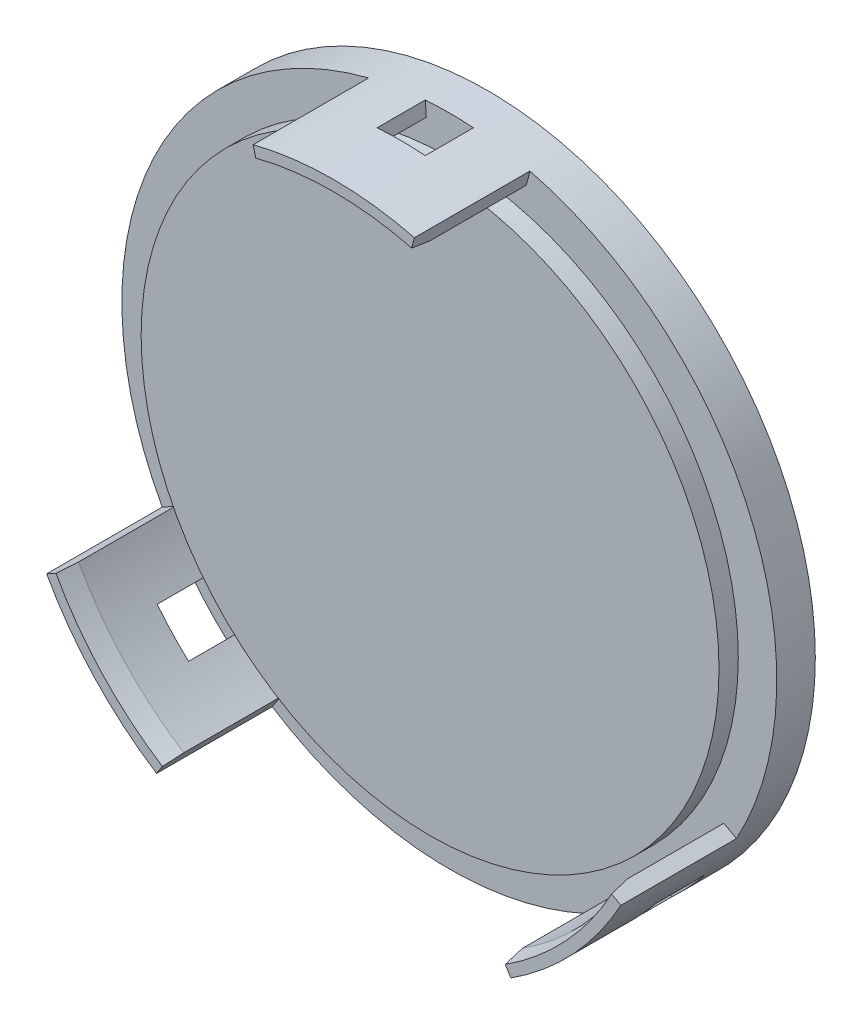
SolidWorks part; units mm, degrees
note: The reader was unsure of these and kept them because the rebuilt part matched: shared geometry of "Sketch1<2>".
ref_plane "Front Plane" through (0, 0, 0) normal (0, 0, 1) x (1, 0, 0)
ref_plane "Top Plane" through (0, 0, 0) normal (0, 1, 0) x (1, 0, 0)
ref_plane "Right Plane" through (0, 0, 0) normal (1, 0, 0) x (0, 0, -1)
sketch "Sketch1" plane through (0, 0, 0) normal (0, 0, 1) x (1, 0, 0)
  circle A0 centre (0, 0) radius 17
  circle A1 centre (0, 0) radius 15
  dimension "D1" = 34
  dimension "D2" = 2
extrude "Boss-Extrude1" add sketch "Sketch1" along normal blind 2
extrude "Boss-Extrude2" add sketch "Sketch1<2>" along normal offset from surface (3 mm away) 1 contours A1 up to face at (17, 0, 2) offset beyond the face yes
sketch "Sketch1<2>" plane through (0, 0, 0) normal (0, 0, 1) x (1, 0, 0) same geometry as "Sketch1"
sketch "Sketch2" plane through (0, 0, 2) normal (0, 0, 1) x (1, 0, 0)
  line L0 (-4.1846, 16.4769) -> (-4, 15.75)
  line L1 (4.1846, 16.4769) -> (4, 15.75)
  circle A0 centre (0, 0) radius 17 construction
  arc A1 (-4, 15.75) -> (4, 15.75) centre (0, 0) cw
  circle A3 centre (0, 0) radius 17
  arc A4 (-4.1846, 16.4769) -> (4.1846, 16.4769) centre (0, 0) ccw
  circle M3 centre (0, 0) radius 17
  dimension "D1" = 0.75
  dimension "D2" = 8
  dimension "D3" = 0
extrude "Boss-Extrude3" add sketch "Sketch2" along normal blind 6 contours L0 A1 L1 M3
sketch "Sketch3" plane through (0, 0, 8) normal (0, 0, 1) x (1, 0, 0)
  line L0 (-1.25, 16.954) -> (-1.1949, 16.206)
  line L1 (1.25, 16.954) -> (1.1949, 16.206)
  arc A0 (4.1846, 16.4769) -> (-4.1846, 16.4769) centre (0, 0) ccw construction
  arc A1 (4, 15.75) -> (-4, 15.75) centre (0, 0) ccw construction
  arc A2 (4, 15.75) -> (-4, 15.75) centre (0, 0) ccw construction
  arc M4 (-4, 15.75) -> (4, 15.75) centre (0, 0) cw
  arc M6 (4.1846, 16.4769) -> (-4.1846, 16.4769) centre (0, 0) ccw
  dimension "D1" = 2.5
extrude "Cut-Extrude1" cut sketch "Sketch3" along normal blind 2.5 from surface at -6 contours L1 L0 M6 M4 starting at face at (15, 0, 2)
chamfer "Chamfer1" distance 1 distance2 0.2 1 edges at (0, 16.25, 8)
pattern_circular "CirPattern1" count 2 every 133 about axis through (0, 0, 0) along (0, 0, 1) of "Boss-Extrude3", "Cut-Extrude1", "Chamfer1"
ref_plane "Plane1" through (0, 0, 0) normal (1, 0, 0) x (0, 0, -1)
ref_plane "Plane2" through (0, 0, 0) normal (0.9537, 0.3007, 0) x (0, 0, -1)
